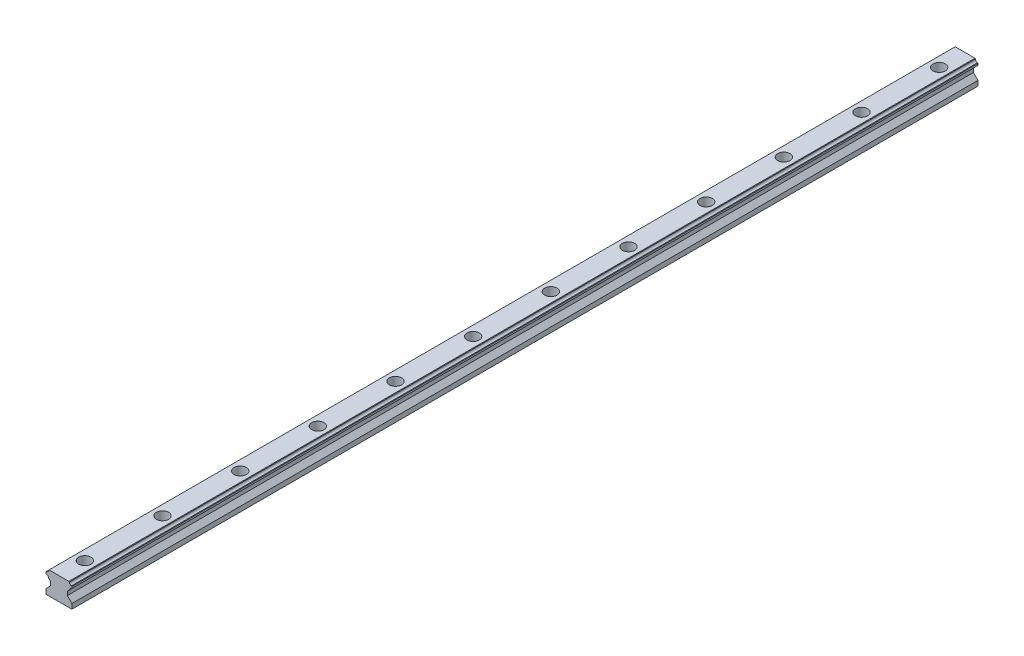
SolidWorks part; units mm, degrees
material "Plain Carbon Steel"
ref_plane "Front Plane" through (0, 0, 0) normal (0, 0, 1) x (1, 0, 0)
ref_plane "Top Plane" through (0, 0, 0) normal (0, 1, 0) x (1, 0, 0)
ref_plane "Right Plane" through (0, 0, 0) normal (1, 0, 0) x (0, 0, -1)
sketch "Sketch1" plane through (0, 0, 0) normal (0, 0, 1) x (1, 0, 0)
  line L0 (0, 13.3681) -> (0, -3.2505) construction
  line L1 (-6.5, -4.15) -> (-6.5, -7.15)
  line L3 (-6.5, -7.15) -> (-10, -10.65)
  line L4 (-10, -10.65) -> (-10, -14.5)
  line L5 (-8.0036, 2.6464) -> (-9.6464, 2.6464) construction
  line L6 (-10, -14.5) -> (0, -14.5)
  line L7 (-6.5, -4.15) -> (-8.0036, -2.6464)
  line L8 (-10, -0.65) -> (-10, 0.65)
  line L9 (-10, 0.65) -> (-9.6464, 1.0036)
  line L10 (-7.65, 3) -> (0, 3)
  line L11 (-10, -0.65) -> (-10, -10.65) construction
  line L12 (-10, 0) -> (0, 0) construction
  line L13 (-8.0036, 2.6464) -> (-7.65, 3)
  line L14 (-9.6464, -1.0036) -> (-10, -0.65)
  line L15 (0, 3) -> (0, -14.5)
  line L16 (-9.6464, 2.6464) -> (-9.6464, 1.0036) construction
  arc A0 (-9.6464, 1.0036) -> (-8.0036, 2.6464) centre (-9.6464, 2.6464) ccw
  arc A1 (-9.6464, -1.0036) -> (-8.0036, -2.6464) centre (-9.6464, -2.6464) cw
  dimension "D5" = 0.5
  dimension "D1" = 14.5
  dimension "D2" = 3
  dimension "D3" = 7.65
  dimension "D4" = 10
  dimension "D6" = 1.3
  dimension "D7" = 17.5
  dimension "D8" = 6.5
  dimension "D9" = 45
extrude "Boss-Extrude1" add sketch "Sketch1" along normal blind 350
mirror "Mirror1" about plane through (0, 3, 350) normal (-1, 0, 0) of "Boss-Extrude1"
sketch "Sketch2" plane through (0, 3, 0) normal (0, 1, 0) x (1, 0, 0)
  line L0 (0, 130.187) -> (0, 31.9327) construction
  line L1 (7.65, 0) -> (-7.65, 0) construction
  circle A0 centre (0, -30) radius 3
  dimension "D1" = 6
  dimension "D2" = 30
extrude "Cut-Extrude1" cut sketch "Sketch2" against normal through all
sketch "Sketch3" plane through (0, 3, 0) normal (0, 1, 0) x (1, 0, 0)
  circle A0 centre (0, -30) radius 4.75
  dimension "D1" = 9.5
extrude "Cut-Extrude2" cut sketch "Sketch3" against normal blind 8.5
pattern_linear "LPattern1" count 100 spacing 60 along (0, 0, 1) of "Cut-Extrude1", "Cut-Extrude2"
mirror "Mirror2" about plane through (-9.6464, -2.6464, 0) normal (0, 0, -1) of bodies 106
equation "\"length\"= 700mm"
equation "\"D1@Boss-Extrude1\" = (\"work_area_depth\" - 200) / 2"
equation "\"M5_tap\"=4.2mm\t\t\t\t\t\t\t' Below you can do mesurements as follows: cm, mm, ft, in, m, "
equation "\"M5_clearence\"=5.5mm"
equation "\"M6_tap\"=5mm"
equation "\"M6_clearence\"=6.6mm"
equation "\"work_area_width\"=1100mm"
equation "\"work_area_depth\"=900mm"
